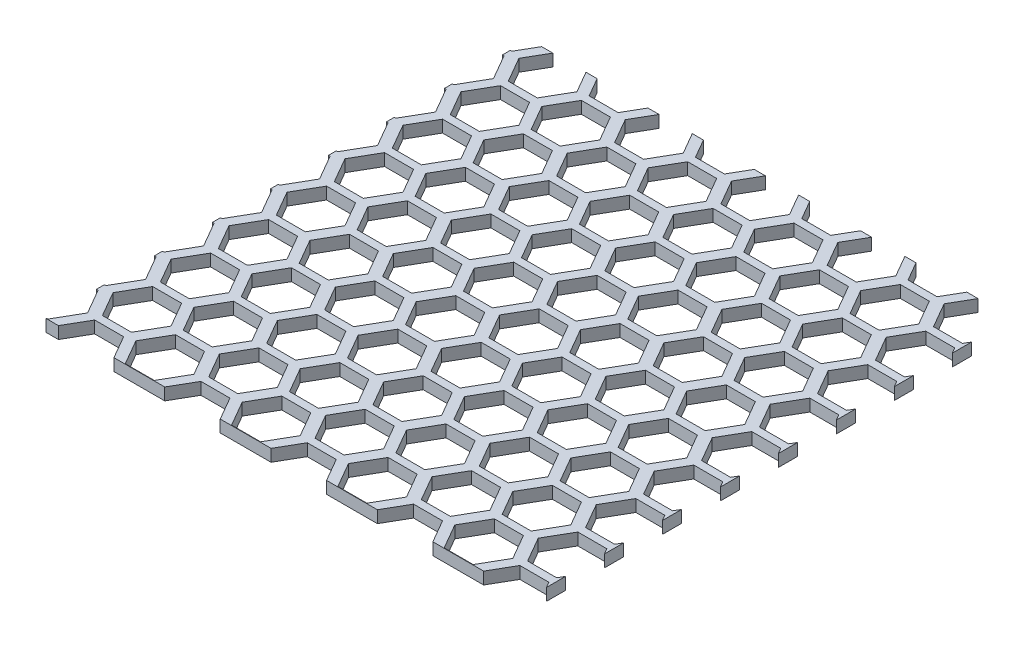
SolidWorks part; units mm, degrees
ref_plane "Front Plane" through (0, 0, 0) normal (0, 0, 1) x (1, 0, 0)
ref_plane "Top Plane" through (0, 0, 0) normal (0, 1, 0) x (1, 0, 0)
ref_plane "Right Plane" through (0, 0, 0) normal (1, 0, 0) x (0, 0, -1)
sketch "Sketch3" plane through (0, 0, 0) normal (0, 1, 0) x (1, 0, 0)
  line L0 (-647.1314, 0) -> (647.1314, 0) construction
  line L1 (131.9336, 512.7952) -> (101.9336, 564.7567)
  line L2 (101.9336, 564.7567) -> (41.9336, 564.7567)
  line L3 (41.9336, 564.7567) -> (11.9336, 512.7952)
  line L4 (11.9336, 512.7952) -> (41.9336, 460.8337)
  line L5 (41.9336, 460.8337) -> (101.9336, 460.8337)
  line L6 (101.9336, 460.8337) -> (131.9336, 512.7952)
  line L7 (241.9336, 455.4747) -> (211.9336, 507.4362)
  line L8 (211.9336, 507.4362) -> (151.9336, 507.4362)
  line L9 (151.9336, 507.4362) -> (121.9336, 455.4747)
  line L10 (121.9336, 455.4747) -> (151.9336, 403.5132)
  line L11 (151.9336, 403.5132) -> (211.9336, 403.5132)
  line L12 (211.9336, 403.5132) -> (241.9336, 455.4747)
  line L13 (351.9336, 512.7952) -> (321.9336, 564.7567)
  line L14 (321.9336, 564.7567) -> (261.9336, 564.7567)
  line L15 (261.9336, 564.7567) -> (231.9336, 512.7952)
  line L16 (231.9336, 512.7952) -> (261.9336, 460.8337)
  line L17 (261.9336, 460.8337) -> (321.9336, 460.8337)
  line L18 (321.9336, 460.8337) -> (351.9336, 512.7952)
  line L19 (461.9336, 455.4747) -> (431.9336, 507.4362)
  line L20 (431.9336, 507.4362) -> (371.9336, 507.4362)
  line L21 (371.9336, 507.4362) -> (341.9336, 455.4747)
  line L22 (341.9336, 455.4747) -> (371.9336, 403.5132)
  line L23 (371.9336, 403.5132) -> (431.9336, 403.5132)
  line L24 (431.9336, 403.5132) -> (461.9336, 455.4747)
  line L25 (571.9336, 512.7952) -> (541.9336, 564.7567)
  line L26 (541.9336, 564.7567) -> (481.9336, 564.7567)
  line L27 (481.9336, 564.7567) -> (451.9336, 512.7952)
  line L28 (451.9336, 512.7952) -> (481.9336, 460.8337)
  line L29 (481.9336, 460.8337) -> (541.9336, 460.8337)
  line L30 (541.9336, 460.8337) -> (571.9336, 512.7952)
  line L31 (681.9336, 455.4747) -> (651.9336, 507.4362)
  line L32 (651.9336, 507.4362) -> (591.9336, 507.4362)
  line L33 (591.9336, 507.4362) -> (561.9336, 455.4747)
  line L34 (561.9336, 455.4747) -> (591.9336, 403.5132)
  line L35 (591.9336, 403.5132) -> (651.9336, 403.5132)
  line L36 (651.9336, 403.5132) -> (681.9336, 455.4747)
  line L37 (791.9336, 512.7952) -> (761.9336, 564.7567)
  line L38 (761.9336, 564.7567) -> (701.9336, 564.7567)
  line L39 (701.9336, 564.7567) -> (671.9336, 512.7952)
  line L40 (671.9336, 512.7952) -> (701.9336, 460.8337)
  line L41 (701.9336, 460.8337) -> (761.9336, 460.8337)
  line L42 (761.9336, 460.8337) -> (791.9336, 512.7952)
  line L43 (901.9336, 455.4747) -> (871.9336, 507.4362)
  line L44 (871.9336, 507.4362) -> (811.9336, 507.4362)
  line L45 (811.9336, 507.4362) -> (781.9336, 455.4747)
  line L46 (781.9336, 455.4747) -> (811.9336, 403.5132)
  line L47 (811.9336, 403.5132) -> (871.9336, 403.5132)
  line L48 (871.9336, 403.5132) -> (901.9336, 455.4747)
  line L49 (1011.9336, 512.7952) -> (981.9336, 564.7567)
  line L50 (981.9336, 564.7567) -> (921.9336, 564.7567)
  line L51 (921.9336, 564.7567) -> (891.9336, 512.7952)
  line L52 (891.9336, 512.7952) -> (921.9336, 460.8337)
  line L53 (921.9336, 460.8337) -> (981.9336, 460.8337)
  line L54 (981.9336, 460.8337) -> (1011.9336, 512.7952)
  line L55 (1121.9336, 455.4747) -> (1091.9336, 507.4362)
  line L56 (1091.9336, 507.4362) -> (1031.9336, 507.4362)
  line L57 (1031.9336, 507.4362) -> (1001.9336, 455.4747)
  line L58 (1001.9336, 455.4747) -> (1031.9336, 403.5132)
  line L59 (1031.9336, 403.5132) -> (1091.9336, 403.5132)
  line L60 (1091.9336, 403.5132) -> (1121.9336, 455.4747)
  line L61 (1231.9336, 512.7952) -> (1201.9336, 564.7567)
  line L62 (1201.9336, 564.7567) -> (1141.9336, 564.7567)
  line L63 (1141.9336, 564.7567) -> (1111.9336, 512.7952)
  line L64 (1111.9336, 512.7952) -> (1141.9336, 460.8337)
  line L65 (1141.9336, 460.8337) -> (1201.9336, 460.8337)
  line L66 (1201.9336, 460.8337) -> (1231.9336, 512.7952)
  line L67 (1341.9336, 455.4747) -> (1311.9336, 507.4362)
  line L68 (1311.9336, 507.4362) -> (1251.9336, 507.4362)
  line L69 (1251.9336, 507.4362) -> (1221.9336, 455.4747)
  line L70 (1221.9336, 455.4747) -> (1251.9336, 403.5132)
  line L71 (1251.9336, 403.5132) -> (1311.9336, 403.5132)
  line L72 (1311.9336, 403.5132) -> (1341.9336, 455.4747)
  line L73 (351.9336, 392.7952) -> (321.9336, 444.7567)
  line L74 (321.9336, 444.7567) -> (261.9336, 444.7567)
  line L75 (261.9336, 444.7567) -> (231.9336, 392.7952)
  line L76 (231.9336, 392.7952) -> (261.9336, 340.8337)
  line L77 (261.9336, 340.8337) -> (321.9336, 340.8337)
  line L78 (321.9336, 340.8337) -> (351.9336, 392.7952)
  line L79 (461.9336, 335.4747) -> (431.9336, 387.4362)
  line L80 (431.9336, 387.4362) -> (371.9336, 387.4362)
  line L81 (371.9336, 387.4362) -> (341.9336, 335.4747)
  line L82 (341.9336, 335.4747) -> (371.9336, 283.5132)
  line L83 (371.9336, 283.5132) -> (431.9336, 283.5132)
  line L84 (431.9336, 283.5132) -> (461.9336, 335.4747)
  line L85 (571.9336, 392.7952) -> (541.9336, 444.7567)
  line L86 (541.9336, 444.7567) -> (481.9336, 444.7567)
  line L87 (481.9336, 444.7567) -> (451.9336, 392.7952)
  line L88 (451.9336, 392.7952) -> (481.9336, 340.8337)
  line L89 (481.9336, 340.8337) -> (541.9336, 340.8337)
  line L90 (541.9336, 340.8337) -> (571.9336, 392.7952)
  line L91 (681.9336, 335.4747) -> (651.9336, 387.4362)
  line L92 (651.9336, 387.4362) -> (591.9336, 387.4362)
  line L93 (591.9336, 387.4362) -> (561.9336, 335.4747)
  line L94 (561.9336, 335.4747) -> (591.9336, 283.5132)
  line L95 (591.9336, 283.5132) -> (651.9336, 283.5132)
  line L96 (651.9336, 283.5132) -> (681.9336, 335.4747)
  line L97 (791.9336, 392.7952) -> (761.9336, 444.7567)
  line L98 (761.9336, 444.7567) -> (701.9336, 444.7567)
  line L99 (701.9336, 444.7567) -> (671.9336, 392.7952)
  line L100 (671.9336, 392.7952) -> (701.9336, 340.8337)
  line L101 (701.9336, 340.8337) -> (761.9336, 340.8337)
  line L102 (761.9336, 340.8337) -> (791.9336, 392.7952)
  line L103 (901.9336, 335.4747) -> (871.9336, 387.4362)
  line L104 (871.9336, 387.4362) -> (811.9336, 387.4362)
  line L105 (811.9336, 387.4362) -> (781.9336, 335.4747)
  line L106 (781.9336, 335.4747) -> (811.9336, 283.5132)
  line L107 (811.9336, 283.5132) -> (871.9336, 283.5132)
  line L108 (871.9336, 283.5132) -> (901.9336, 335.4747)
  line L109 (1011.9336, 392.7952) -> (981.9336, 444.7567)
  line L110 (981.9336, 444.7567) -> (921.9336, 444.7567)
  line L111 (921.9336, 444.7567) -> (891.9336, 392.7952)
  line L112 (891.9336, 392.7952) -> (921.9336, 340.8337)
  line L113 (921.9336, 340.8337) -> (981.9336, 340.8337)
  line L114 (981.9336, 340.8337) -> (1011.9336, 392.7952)
  line L115 (1121.9336, 335.4747) -> (1091.9336, 387.4362)
  line L116 (1091.9336, 387.4362) -> (1031.9336, 387.4362)
  line L117 (1031.9336, 387.4362) -> (1001.9336, 335.4747)
  line L118 (1001.9336, 335.4747) -> (1031.9336, 283.5132)
  line L119 (1031.9336, 283.5132) -> (1091.9336, 283.5132)
  line L120 (1091.9336, 283.5132) -> (1121.9336, 335.4747)
  line L121 (1231.9336, 392.7952) -> (1201.9336, 444.7567)
  line L122 (1201.9336, 444.7567) -> (1141.9336, 444.7567)
  line L123 (1141.9336, 444.7567) -> (1111.9336, 392.7952)
  line L124 (1111.9336, 392.7952) -> (1141.9336, 340.8337)
  line L125 (1141.9336, 340.8337) -> (1201.9336, 340.8337)
  line L126 (1201.9336, 340.8337) -> (1231.9336, 392.7952)
  line L127 (1341.9336, 335.4747) -> (1311.9336, 387.4362)
  line L128 (1311.9336, 387.4362) -> (1251.9336, 387.4362)
  line L129 (1251.9336, 387.4362) -> (1221.9336, 335.4747)
  line L130 (1221.9336, 335.4747) -> (1251.9336, 283.5132)
  line L131 (1251.9336, 283.5132) -> (1311.9336, 283.5132)
  line L132 (1311.9336, 283.5132) -> (1341.9336, 335.4747)
  line L133 (351.9336, 272.7952) -> (321.9336, 324.7567)
  line L134 (321.9336, 324.7567) -> (261.9336, 324.7567)
  line L135 (261.9336, 324.7567) -> (231.9336, 272.7952)
  line L136 (231.9336, 272.7952) -> (261.9336, 220.8337)
  line L137 (261.9336, 220.8337) -> (321.9336, 220.8337)
  line L138 (321.9336, 220.8337) -> (351.9336, 272.7952)
  line L139 (461.9336, 215.4747) -> (431.9336, 267.4362)
  line L140 (431.9336, 267.4362) -> (371.9336, 267.4362)
  line L141 (371.9336, 267.4362) -> (341.9336, 215.4747)
  line L142 (341.9336, 215.4747) -> (371.9336, 163.5132)
  line L143 (371.9336, 163.5132) -> (431.9336, 163.5132)
  line L144 (431.9336, 163.5132) -> (461.9336, 215.4747)
  line L145 (571.9336, 272.7952) -> (541.9336, 324.7567)
  line L146 (541.9336, 324.7567) -> (481.9336, 324.7567)
  line L147 (481.9336, 324.7567) -> (451.9336, 272.7952)
  line L148 (451.9336, 272.7952) -> (481.9336, 220.8337)
  line L149 (481.9336, 220.8337) -> (541.9336, 220.8337)
  line L150 (541.9336, 220.8337) -> (571.9336, 272.7952)
  line L151 (681.9336, 215.4747) -> (651.9336, 267.4362)
  line L152 (651.9336, 267.4362) -> (591.9336, 267.4362)
  line L153 (591.9336, 267.4362) -> (561.9336, 215.4747)
  line L154 (561.9336, 215.4747) -> (591.9336, 163.5132)
  line L155 (591.9336, 163.5132) -> (651.9336, 163.5132)
  line L156 (651.9336, 163.5132) -> (681.9336, 215.4747)
  line L157 (791.9336, 272.7952) -> (761.9336, 324.7567)
  line L158 (761.9336, 324.7567) -> (701.9336, 324.7567)
  line L159 (701.9336, 324.7567) -> (671.9336, 272.7952)
  line L160 (671.9336, 272.7952) -> (701.9336, 220.8337)
  line L161 (701.9336, 220.8337) -> (761.9336, 220.8337)
  line L162 (761.9336, 220.8337) -> (791.9336, 272.7952)
  line L163 (901.9336, 215.4747) -> (871.9336, 267.4362)
  line L164 (871.9336, 267.4362) -> (811.9336, 267.4362)
  line L165 (811.9336, 267.4362) -> (781.9336, 215.4747)
  line L166 (781.9336, 215.4747) -> (811.9336, 163.5132)
  line L167 (811.9336, 163.5132) -> (871.9336, 163.5132)
  line L168 (871.9336, 163.5132) -> (901.9336, 215.4747)
  line L169 (1011.9336, 272.7952) -> (981.9336, 324.7567)
  line L170 (981.9336, 324.7567) -> (921.9336, 324.7567)
  line L171 (921.9336, 324.7567) -> (891.9336, 272.7952)
  line L172 (891.9336, 272.7952) -> (921.9336, 220.8337)
  line L173 (921.9336, 220.8337) -> (981.9336, 220.8337)
  line L174 (981.9336, 220.8337) -> (1011.9336, 272.7952)
  line L175 (1121.9336, 215.4747) -> (1091.9336, 267.4362)
  line L176 (1091.9336, 267.4362) -> (1031.9336, 267.4362)
  line L177 (1031.9336, 267.4362) -> (1001.9336, 215.4747)
  line L178 (1001.9336, 215.4747) -> (1031.9336, 163.5132)
  line L179 (1031.9336, 163.5132) -> (1091.9336, 163.5132)
  line L180 (1091.9336, 163.5132) -> (1121.9336, 215.4747)
  line L181 (1231.9336, 272.7952) -> (1201.9336, 324.7567)
  line L182 (1201.9336, 324.7567) -> (1141.9336, 324.7567)
  line L183 (1141.9336, 324.7567) -> (1111.9336, 272.7952)
  line L184 (1111.9336, 272.7952) -> (1141.9336, 220.8337)
  line L185 (1141.9336, 220.8337) -> (1201.9336, 220.8337)
  line L186 (1201.9336, 220.8337) -> (1231.9336, 272.7952)
  line L187 (1341.9336, 215.4747) -> (1311.9336, 267.4362)
  line L188 (1311.9336, 267.4362) -> (1251.9336, 267.4362)
  line L189 (1251.9336, 267.4362) -> (1221.9336, 215.4747)
  line L190 (1221.9336, 215.4747) -> (1251.9336, 163.5132)
  line L191 (1251.9336, 163.5132) -> (1311.9336, 163.5132)
  line L192 (1311.9336, 163.5132) -> (1341.9336, 215.4747)
  line L193 (351.9336, 152.7952) -> (321.9336, 204.7567)
  line L194 (321.9336, 204.7567) -> (261.9336, 204.7567)
  line L195 (261.9336, 204.7567) -> (231.9336, 152.7952)
  line L196 (231.9336, 152.7952) -> (261.9336, 100.8337)
  line L197 (261.9336, 100.8337) -> (321.9336, 100.8337)
  line L198 (321.9336, 100.8337) -> (351.9336, 152.7952)
  line L199 (461.9336, 95.4747) -> (431.9336, 147.4362)
  line L200 (431.9336, 147.4362) -> (371.9336, 147.4362)
  line L201 (371.9336, 147.4362) -> (341.9336, 95.4747)
  line L202 (341.9336, 95.4747) -> (371.9336, 43.5132)
  line L203 (371.9336, 43.5132) -> (431.9336, 43.5132)
  line L204 (431.9336, 43.5132) -> (461.9336, 95.4747)
  line L205 (571.9336, 152.7952) -> (541.9336, 204.7567)
  line L206 (541.9336, 204.7567) -> (481.9336, 204.7567)
  line L207 (481.9336, 204.7567) -> (451.9336, 152.7952)
  line L208 (451.9336, 152.7952) -> (481.9336, 100.8337)
  line L209 (481.9336, 100.8337) -> (541.9336, 100.8337)
  line L210 (541.9336, 100.8337) -> (571.9336, 152.7952)
  line L211 (681.9336, 95.4747) -> (651.9336, 147.4362)
  line L212 (651.9336, 147.4362) -> (591.9336, 147.4362)
  line L213 (591.9336, 147.4362) -> (561.9336, 95.4747)
  line L214 (561.9336, 95.4747) -> (591.9336, 43.5132)
  line L215 (591.9336, 43.5132) -> (651.9336, 43.5132)
  line L216 (651.9336, 43.5132) -> (681.9336, 95.4747)
  line L217 (791.9336, 152.7952) -> (761.9336, 204.7567)
  line L218 (761.9336, 204.7567) -> (701.9336, 204.7567)
  line L219 (701.9336, 204.7567) -> (671.9336, 152.7952)
  line L220 (671.9336, 152.7952) -> (701.9336, 100.8337)
  line L221 (701.9336, 100.8337) -> (761.9336, 100.8337)
  line L222 (761.9336, 100.8337) -> (791.9336, 152.7952)
  line L223 (901.9336, 95.4747) -> (871.9336, 147.4362)
  line L224 (871.9336, 147.4362) -> (811.9336, 147.4362)
  line L225 (811.9336, 147.4362) -> (781.9336, 95.4747)
  line L226 (781.9336, 95.4747) -> (811.9336, 43.5132)
  line L227 (811.9336, 43.5132) -> (871.9336, 43.5132)
  line L228 (871.9336, 43.5132) -> (901.9336, 95.4747)
  line L229 (1011.9336, 152.7952) -> (981.9336, 204.7567)
  line L230 (981.9336, 204.7567) -> (921.9336, 204.7567)
  line L231 (921.9336, 204.7567) -> (891.9336, 152.7952)
  line L232 (891.9336, 152.7952) -> (921.9336, 100.8337)
  line L233 (921.9336, 100.8337) -> (981.9336, 100.8337)
  line L234 (981.9336, 100.8337) -> (1011.9336, 152.7952)
  line L235 (1121.9336, 95.4747) -> (1091.9336, 147.4362)
  line L236 (1091.9336, 147.4362) -> (1031.9336, 147.4362)
  line L237 (1031.9336, 147.4362) -> (1001.9336, 95.4747)
  line L238 (1001.9336, 95.4747) -> (1031.9336, 43.5132)
  line L239 (1031.9336, 43.5132) -> (1091.9336, 43.5132)
  line L240 (1091.9336, 43.5132) -> (1121.9336, 95.4747)
  line L241 (1231.9336, 152.7952) -> (1201.9336, 204.7567)
  line L242 (1201.9336, 204.7567) -> (1141.9336, 204.7567)
  line L243 (1141.9336, 204.7567) -> (1111.9336, 152.7952)
  line L244 (1111.9336, 152.7952) -> (1141.9336, 100.8337)
  line L245 (1141.9336, 100.8337) -> (1201.9336, 100.8337)
  line L246 (1201.9336, 100.8337) -> (1231.9336, 152.7952)
  line L247 (1341.9336, 95.4747) -> (1311.9336, 147.4362)
  line L248 (1311.9336, 147.4362) -> (1251.9336, 147.4362)
  line L249 (1251.9336, 147.4362) -> (1221.9336, 95.4747)
  line L250 (1221.9336, 95.4747) -> (1251.9336, 43.5132)
  line L251 (1251.9336, 43.5132) -> (1311.9336, 43.5132)
  line L252 (1311.9336, 43.5132) -> (1341.9336, 95.4747)
  line L253 (351.9336, 32.7952) -> (321.9336, 84.7567)
  line L254 (321.9336, 84.7567) -> (261.9336, 84.7567)
  line L255 (261.9336, 84.7567) -> (231.9336, 32.7952)
  line L256 (231.9336, 32.7952) -> (261.9336, -19.1663)
  line L257 (261.9336, -19.1663) -> (321.9336, -19.1663)
  line L258 (321.9336, -19.1663) -> (351.9336, 32.7952)
  line L259 (461.9336, -24.5253) -> (431.9336, 27.4362)
  line L260 (431.9336, 27.4362) -> (371.9336, 27.4362)
  line L261 (371.9336, 27.4362) -> (341.9336, -24.5253)
  line L262 (341.9336, -24.5253) -> (371.9336, -76.4868)
  line L263 (371.9336, -76.4868) -> (431.9336, -76.4868)
  line L264 (431.9336, -76.4868) -> (461.9336, -24.5253)
  line L265 (571.9336, 32.7952) -> (541.9336, 84.7567)
  line L266 (541.9336, 84.7567) -> (481.9336, 84.7567)
  line L267 (481.9336, 84.7567) -> (451.9336, 32.7952)
  line L268 (451.9336, 32.7952) -> (481.9336, -19.1663)
  line L269 (481.9336, -19.1663) -> (541.9336, -19.1663)
  line L270 (541.9336, -19.1663) -> (571.9336, 32.7952)
  line L271 (681.9336, -24.5253) -> (651.9336, 27.4362)
  line L272 (651.9336, 27.4362) -> (591.9336, 27.4362)
  line L273 (591.9336, 27.4362) -> (561.9336, -24.5253)
  line L274 (561.9336, -24.5253) -> (591.9336, -76.4868)
  line L275 (591.9336, -76.4868) -> (651.9336, -76.4868)
  line L276 (651.9336, -76.4868) -> (681.9336, -24.5253)
  line L277 (791.9336, 32.7952) -> (761.9336, 84.7567)
  line L278 (761.9336, 84.7567) -> (701.9336, 84.7567)
  line L279 (701.9336, 84.7567) -> (671.9336, 32.7952)
  line L280 (671.9336, 32.7952) -> (701.9336, -19.1663)
  line L281 (701.9336, -19.1663) -> (761.9336, -19.1663)
  line L282 (761.9336, -19.1663) -> (791.9336, 32.7952)
  line L283 (901.9336, -24.5253) -> (871.9336, 27.4362)
  line L284 (871.9336, 27.4362) -> (811.9336, 27.4362)
  line L285 (811.9336, 27.4362) -> (781.9336, -24.5253)
  line L286 (781.9336, -24.5253) -> (811.9336, -76.4868)
  line L287 (811.9336, -76.4868) -> (871.9336, -76.4868)
  line L288 (871.9336, -76.4868) -> (901.9336, -24.5253)
  line L289 (1011.9336, 32.7952) -> (981.9336, 84.7567)
  line L290 (981.9336, 84.7567) -> (921.9336, 84.7567)
  line L291 (921.9336, 84.7567) -> (891.9336, 32.7952)
  line L292 (891.9336, 32.7952) -> (921.9336, -19.1663)
  line L293 (921.9336, -19.1663) -> (981.9336, -19.1663)
  line L294 (981.9336, -19.1663) -> (1011.9336, 32.7952)
  line L295 (1121.9336, -24.5253) -> (1091.9336, 27.4362)
  line L296 (1091.9336, 27.4362) -> (1031.9336, 27.4362)
  line L297 (1031.9336, 27.4362) -> (1001.9336, -24.5253)
  line L298 (1001.9336, -24.5253) -> (1031.9336, -76.4868)
  line L299 (1031.9336, -76.4868) -> (1091.9336, -76.4868)
  line L300 (1091.9336, -76.4868) -> (1121.9336, -24.5253)
  line L301 (1231.9336, 32.7952) -> (1201.9336, 84.7567)
  line L302 (1201.9336, 84.7567) -> (1141.9336, 84.7567)
  line L303 (1141.9336, 84.7567) -> (1111.9336, 32.7952)
  line L304 (1111.9336, 32.7952) -> (1141.9336, -19.1663)
  line L305 (1141.9336, -19.1663) -> (1201.9336, -19.1663)
  line L306 (1201.9336, -19.1663) -> (1231.9336, 32.7952)
  line L307 (1341.9336, -24.5253) -> (1311.9336, 27.4362)
  line L308 (1311.9336, 27.4362) -> (1251.9336, 27.4362)
  line L309 (1251.9336, 27.4362) -> (1221.9336, -24.5253)
  line L310 (1221.9336, -24.5253) -> (1251.9336, -76.4868)
  line L311 (1251.9336, -76.4868) -> (1311.9336, -76.4868)
  line L312 (1311.9336, -76.4868) -> (1341.9336, -24.5253)
  line L313 (351.9336, -87.2048) -> (321.9336, -35.2433)
  line L314 (321.9336, -35.2433) -> (261.9336, -35.2433)
  line L315 (261.9336, -35.2433) -> (231.9336, -87.2048)
  line L316 (231.9336, -87.2048) -> (261.9336, -139.1663)
  line L317 (261.9336, -139.1663) -> (321.9336, -139.1663)
  line L318 (321.9336, -139.1663) -> (351.9336, -87.2048)
  line L319 (461.9336, -144.5253) -> (431.9336, -92.5638)
  line L320 (431.9336, -92.5638) -> (371.9336, -92.5638)
  line L321 (371.9336, -92.5638) -> (341.9336, -144.5253)
  line L322 (341.9336, -144.5253) -> (371.9336, -196.4868)
  line L323 (371.9336, -196.4868) -> (431.9336, -196.4868)
  line L324 (431.9336, -196.4868) -> (461.9336, -144.5253)
  line L325 (571.9336, -87.2048) -> (541.9336, -35.2433)
  line L326 (541.9336, -35.2433) -> (481.9336, -35.2433)
  line L327 (481.9336, -35.2433) -> (451.9336, -87.2048)
  line L328 (451.9336, -87.2048) -> (481.9336, -139.1663)
  line L329 (481.9336, -139.1663) -> (541.9336, -139.1663)
  line L330 (541.9336, -139.1663) -> (571.9336, -87.2048)
  line L331 (681.9336, -144.5253) -> (651.9336, -92.5638)
  line L332 (651.9336, -92.5638) -> (591.9336, -92.5638)
  line L333 (591.9336, -92.5638) -> (561.9336, -144.5253)
  line L334 (561.9336, -144.5253) -> (591.9336, -196.4868)
  line L335 (591.9336, -196.4868) -> (651.9336, -196.4868)
  line L336 (651.9336, -196.4868) -> (681.9336, -144.5253)
  line L337 (791.9336, -87.2048) -> (761.9336, -35.2433)
  line L338 (761.9336, -35.2433) -> (701.9336, -35.2433)
  line L339 (701.9336, -35.2433) -> (671.9336, -87.2048)
  line L340 (671.9336, -87.2048) -> (701.9336, -139.1663)
  line L341 (701.9336, -139.1663) -> (761.9336, -139.1663)
  line L342 (761.9336, -139.1663) -> (791.9336, -87.2048)
  line L343 (901.9336, -144.5253) -> (871.9336, -92.5638)
  line L344 (871.9336, -92.5638) -> (811.9336, -92.5638)
  line L345 (811.9336, -92.5638) -> (781.9336, -144.5253)
  line L346 (781.9336, -144.5253) -> (811.9336, -196.4868)
  line L347 (811.9336, -196.4868) -> (871.9336, -196.4868)
  line L348 (871.9336, -196.4868) -> (901.9336, -144.5253)
  line L349 (1011.9336, -87.2048) -> (981.9336, -35.2433)
  line L350 (981.9336, -35.2433) -> (921.9336, -35.2433)
  line L351 (921.9336, -35.2433) -> (891.9336, -87.2048)
  line L352 (891.9336, -87.2048) -> (921.9336, -139.1663)
  line L353 (921.9336, -139.1663) -> (981.9336, -139.1663)
  line L354 (981.9336, -139.1663) -> (1011.9336, -87.2048)
  line L355 (1121.9336, -144.5253) -> (1091.9336, -92.5638)
  line L356 (1091.9336, -92.5638) -> (1031.9336, -92.5638)
  line L357 (1031.9336, -92.5638) -> (1001.9336, -144.5253)
  line L358 (1001.9336, -144.5253) -> (1031.9336, -196.4868)
  line L359 (1031.9336, -196.4868) -> (1091.9336, -196.4868)
  line L360 (1091.9336, -196.4868) -> (1121.9336, -144.5253)
  line L361 (1231.9336, -87.2048) -> (1201.9336, -35.2433)
  line L362 (1201.9336, -35.2433) -> (1141.9336, -35.2433)
  line L363 (1141.9336, -35.2433) -> (1111.9336, -87.2048)
  line L364 (1111.9336, -87.2048) -> (1141.9336, -139.1663)
  line L365 (1141.9336, -139.1663) -> (1201.9336, -139.1663)
  line L366 (1201.9336, -139.1663) -> (1231.9336, -87.2048)
  line L367 (1341.9336, -144.5253) -> (1311.9336, -92.5638)
  line L368 (1311.9336, -92.5638) -> (1251.9336, -92.5638)
  line L369 (1251.9336, -92.5638) -> (1221.9336, -144.5253)
  line L370 (1221.9336, -144.5253) -> (1251.9336, -196.4868)
  line L371 (1251.9336, -196.4868) -> (1311.9336, -196.4868)
  line L372 (1311.9336, -196.4868) -> (1341.9336, -144.5253)
  line L373 (351.9336, -207.2048) -> (321.9336, -155.2433)
  line L374 (321.9336, -155.2433) -> (261.9336, -155.2433)
  line L375 (261.9336, -155.2433) -> (231.9336, -207.2048)
  line L376 (231.9336, -207.2048) -> (261.9336, -259.1663)
  line L377 (261.9336, -259.1663) -> (321.9336, -259.1663)
  line L378 (321.9336, -259.1663) -> (351.9336, -207.2048)
  line L379 (461.9336, -264.5253) -> (431.9336, -212.5638)
  line L380 (431.9336, -212.5638) -> (371.9336, -212.5638)
  line L381 (371.9336, -212.5638) -> (341.9336, -264.5253)
  line L382 (341.9336, -264.5253) -> (371.9336, -316.4868)
  line L383 (371.9336, -316.4868) -> (431.9336, -316.4868)
  line L384 (431.9336, -316.4868) -> (461.9336, -264.5253)
  line L385 (571.9336, -207.2048) -> (541.9336, -155.2433)
  line L386 (541.9336, -155.2433) -> (481.9336, -155.2433)
  line L387 (481.9336, -155.2433) -> (451.9336, -207.2048)
  line L388 (451.9336, -207.2048) -> (481.9336, -259.1663)
  line L389 (481.9336, -259.1663) -> (541.9336, -259.1663)
  line L390 (541.9336, -259.1663) -> (571.9336, -207.2048)
  line L391 (681.9336, -264.5253) -> (651.9336, -212.5638)
  line L392 (651.9336, -212.5638) -> (591.9336, -212.5638)
  line L393 (591.9336, -212.5638) -> (561.9336, -264.5253)
  line L394 (561.9336, -264.5253) -> (591.9336, -316.4868)
  line L395 (591.9336, -316.4868) -> (651.9336, -316.4868)
  line L396 (651.9336, -316.4868) -> (681.9336, -264.5253)
  line L397 (791.9336, -207.2048) -> (761.9336, -155.2433)
  line L398 (761.9336, -155.2433) -> (701.9336, -155.2433)
  line L399 (701.9336, -155.2433) -> (671.9336, -207.2048)
  line L400 (671.9336, -207.2048) -> (701.9336, -259.1663)
  line L401 (701.9336, -259.1663) -> (761.9336, -259.1663)
  line L402 (761.9336, -259.1663) -> (791.9336, -207.2048)
  line L403 (901.9336, -264.5253) -> (871.9336, -212.5638)
  line L404 (871.9336, -212.5638) -> (811.9336, -212.5638)
  line L405 (811.9336, -212.5638) -> (781.9336, -264.5253)
  line L406 (781.9336, -264.5253) -> (811.9336, -316.4868)
  line L407 (811.9336, -316.4868) -> (871.9336, -316.4868)
  line L408 (871.9336, -316.4868) -> (901.9336, -264.5253)
  line L409 (1011.9336, -207.2048) -> (981.9336, -155.2433)
  line L410 (981.9336, -155.2433) -> (921.9336, -155.2433)
  line L411 (921.9336, -155.2433) -> (891.9336, -207.2048)
  line L412 (891.9336, -207.2048) -> (921.9336, -259.1663)
  line L413 (921.9336, -259.1663) -> (981.9336, -259.1663)
  line L414 (981.9336, -259.1663) -> (1011.9336, -207.2048)
  line L415 (1121.9336, -264.5253) -> (1091.9336, -212.5638)
  line L416 (1091.9336, -212.5638) -> (1031.9336, -212.5638)
  line L417 (1031.9336, -212.5638) -> (1001.9336, -264.5253)
  line L418 (1001.9336, -264.5253) -> (1031.9336, -316.4868)
  line L419 (1031.9336, -316.4868) -> (1091.9336, -316.4868)
  line L420 (1091.9336, -316.4868) -> (1121.9336, -264.5253)
  line L421 (1231.9336, -207.2048) -> (1201.9336, -155.2433)
  line L422 (1201.9336, -155.2433) -> (1141.9336, -155.2433)
  line L423 (1141.9336, -155.2433) -> (1111.9336, -207.2048)
  line L424 (1111.9336, -207.2048) -> (1141.9336, -259.1663)
  line L425 (1141.9336, -259.1663) -> (1201.9336, -259.1663)
  line L426 (1201.9336, -259.1663) -> (1231.9336, -207.2048)
  line L427 (1341.9336, -264.5253) -> (1311.9336, -212.5638)
  line L428 (1311.9336, -212.5638) -> (1251.9336, -212.5638)
  line L429 (1251.9336, -212.5638) -> (1221.9336, -264.5253)
  line L430 (1221.9336, -264.5253) -> (1251.9336, -316.4868)
  line L431 (1251.9336, -316.4868) -> (1311.9336, -316.4868)
  line L432 (1311.9336, -316.4868) -> (1341.9336, -264.5253)
  line L433 (351.9336, -327.2048) -> (321.9336, -275.2433)
  line L434 (321.9336, -275.2433) -> (261.9336, -275.2433)
  line L435 (261.9336, -275.2433) -> (231.9336, -327.2048)
  line L436 (231.9336, -327.2048) -> (261.9336, -379.1663)
  line L437 (261.9336, -379.1663) -> (321.9336, -379.1663)
  line L438 (321.9336, -379.1663) -> (351.9336, -327.2048)
  line L439 (461.9336, -384.5253) -> (431.9336, -332.5638)
  line L440 (431.9336, -332.5638) -> (371.9336, -332.5638)
  line L441 (371.9336, -332.5638) -> (341.9336, -384.5253)
  line L442 (341.9336, -384.5253) -> (371.9336, -436.4868)
  line L443 (371.9336, -436.4868) -> (431.9336, -436.4868)
  line L444 (431.9336, -436.4868) -> (461.9336, -384.5253)
  line L445 (571.9336, -327.2048) -> (541.9336, -275.2433)
  line L446 (541.9336, -275.2433) -> (481.9336, -275.2433)
  line L447 (481.9336, -275.2433) -> (451.9336, -327.2048)
  line L448 (451.9336, -327.2048) -> (481.9336, -379.1663)
  line L449 (481.9336, -379.1663) -> (541.9336, -379.1663)
  line L450 (541.9336, -379.1663) -> (571.9336, -327.2048)
  line L451 (681.9336, -384.5253) -> (651.9336, -332.5638)
  line L452 (651.9336, -332.5638) -> (591.9336, -332.5638)
  line L453 (591.9336, -332.5638) -> (561.9336, -384.5253)
  line L454 (561.9336, -384.5253) -> (591.9336, -436.4868)
  line L455 (591.9336, -436.4868) -> (651.9336, -436.4868)
  line L456 (651.9336, -436.4868) -> (681.9336, -384.5253)
  line L457 (791.9336, -327.2048) -> (761.9336, -275.2433)
  line L458 (761.9336, -275.2433) -> (701.9336, -275.2433)
  line L459 (701.9336, -275.2433) -> (671.9336, -327.2048)
  line L460 (671.9336, -327.2048) -> (701.9336, -379.1663)
  line L461 (701.9336, -379.1663) -> (761.9336, -379.1663)
  line L462 (761.9336, -379.1663) -> (791.9336, -327.2048)
  line L463 (901.9336, -384.5253) -> (871.9336, -332.5638)
  line L464 (871.9336, -332.5638) -> (811.9336, -332.5638)
  line L465 (811.9336, -332.5638) -> (781.9336, -384.5253)
  line L466 (781.9336, -384.5253) -> (811.9336, -436.4868)
  line L467 (811.9336, -436.4868) -> (871.9336, -436.4868)
  line L468 (871.9336, -436.4868) -> (901.9336, -384.5253)
  line L469 (1011.9336, -327.2048) -> (981.9336, -275.2433)
  line L470 (981.9336, -275.2433) -> (921.9336, -275.2433)
  line L471 (921.9336, -275.2433) -> (891.9336, -327.2048)
  line L472 (891.9336, -327.2048) -> (921.9336, -379.1663)
  line L473 (921.9336, -379.1663) -> (981.9336, -379.1663)
  line L474 (981.9336, -379.1663) -> (1011.9336, -327.2048)
  line L475 (1121.9336, -384.5253) -> (1091.9336, -332.5638)
  line L476 (1091.9336, -332.5638) -> (1031.9336, -332.5638)
  line L477 (1031.9336, -332.5638) -> (1001.9336, -384.5253)
  line L478 (1001.9336, -384.5253) -> (1031.9336, -436.4868)
  line L479 (1031.9336, -436.4868) -> (1091.9336, -436.4868)
  line L480 (1091.9336, -436.4868) -> (1121.9336, -384.5253)
  line L481 (1231.9336, -327.2048) -> (1201.9336, -275.2433)
  line L482 (1201.9336, -275.2433) -> (1141.9336, -275.2433)
  line L483 (1141.9336, -275.2433) -> (1111.9336, -327.2048)
  line L484 (1111.9336, -327.2048) -> (1141.9336, -379.1663)
  line L485 (1141.9336, -379.1663) -> (1201.9336, -379.1663)
  line L486 (1201.9336, -379.1663) -> (1231.9336, -327.2048)
  line L487 (1341.9336, -384.5253) -> (1311.9336, -332.5638)
  line L488 (1311.9336, -332.5638) -> (1251.9336, -332.5638)
  line L489 (1251.9336, -332.5638) -> (1221.9336, -384.5253)
  line L490 (1221.9336, -384.5253) -> (1251.9336, -436.4868)
  line L491 (1251.9336, -436.4868) -> (1311.9336, -436.4868)
  line L492 (1311.9336, -436.4868) -> (1341.9336, -384.5253)
  line L493 (351.9336, -447.2048) -> (321.9336, -395.2433)
  line L494 (321.9336, -395.2433) -> (261.9336, -395.2433)
  line L495 (261.9336, -395.2433) -> (231.9336, -447.2048)
  line L496 (231.9336, -447.2048) -> (261.9336, -499.1663)
  line L497 (261.9336, -499.1663) -> (321.9336, -499.1663)
  line L498 (321.9336, -499.1663) -> (351.9336, -447.2048)
  line L499 (461.9336, -504.5253) -> (431.9336, -452.5638)
  line L500 (431.9336, -452.5638) -> (371.9336, -452.5638)
  line L501 (371.9336, -452.5638) -> (341.9336, -504.5253)
  line L502 (341.9336, -504.5253) -> (371.9336, -556.4868)
  line L503 (371.9336, -556.4868) -> (431.9336, -556.4868)
  line L504 (431.9336, -556.4868) -> (461.9336, -504.5253)
  line L505 (571.9336, -447.2048) -> (541.9336, -395.2433)
  line L506 (541.9336, -395.2433) -> (481.9336, -395.2433)
  line L507 (481.9336, -395.2433) -> (451.9336, -447.2048)
  line L508 (451.9336, -447.2048) -> (481.9336, -499.1663)
  line L509 (481.9336, -499.1663) -> (541.9336, -499.1663)
  line L510 (541.9336, -499.1663) -> (571.9336, -447.2048)
  line L511 (681.9336, -504.5253) -> (651.9336, -452.5638)
  line L512 (651.9336, -452.5638) -> (591.9336, -452.5638)
  line L513 (591.9336, -452.5638) -> (561.9336, -504.5253)
  line L514 (561.9336, -504.5253) -> (591.9336, -556.4868)
  line L515 (591.9336, -556.4868) -> (651.9336, -556.4868)
  line L516 (651.9336, -556.4868) -> (681.9336, -504.5253)
  line L517 (791.9336, -447.2048) -> (761.9336, -395.2433)
  line L518 (761.9336, -395.2433) -> (701.9336, -395.2433)
  line L519 (701.9336, -395.2433) -> (671.9336, -447.2048)
  line L520 (671.9336, -447.2048) -> (701.9336, -499.1663)
  line L521 (701.9336, -499.1663) -> (761.9336, -499.1663)
  line L522 (761.9336, -499.1663) -> (791.9336, -447.2048)
  line L523 (901.9336, -504.5253) -> (871.9336, -452.5638)
  line L524 (871.9336, -452.5638) -> (811.9336, -452.5638)
  line L525 (811.9336, -452.5638) -> (781.9336, -504.5253)
  line L526 (781.9336, -504.5253) -> (811.9336, -556.4868)
  line L527 (811.9336, -556.4868) -> (871.9336, -556.4868)
  line L528 (871.9336, -556.4868) -> (901.9336, -504.5253)
  line L529 (1011.9336, -447.2048) -> (981.9336, -395.2433)
  line L530 (981.9336, -395.2433) -> (921.9336, -395.2433)
  line L531 (921.9336, -395.2433) -> (891.9336, -447.2048)
  line L532 (891.9336, -447.2048) -> (921.9336, -499.1663)
  line L533 (921.9336, -499.1663) -> (981.9336, -499.1663)
  line L534 (981.9336, -499.1663) -> (1011.9336, -447.2048)
  line L535 (1121.9336, -504.5253) -> (1091.9336, -452.5638)
  line L536 (1091.9336, -452.5638) -> (1031.9336, -452.5638)
  line L537 (1031.9336, -452.5638) -> (1001.9336, -504.5253)
  line L538 (1001.9336, -504.5253) -> (1031.9336, -556.4868)
  line L539 (1031.9336, -556.4868) -> (1091.9336, -556.4868)
  line L540 (1091.9336, -556.4868) -> (1121.9336, -504.5253)
  line L541 (1231.9336, -447.2048) -> (1201.9336, -395.2433)
  line L542 (1201.9336, -395.2433) -> (1141.9336, -395.2433)
  line L543 (1141.9336, -395.2433) -> (1111.9336, -447.2048)
  line L544 (1111.9336, -447.2048) -> (1141.9336, -499.1663)
  line L545 (1141.9336, -499.1663) -> (1201.9336, -499.1663)
  line L546 (1201.9336, -499.1663) -> (1231.9336, -447.2048)
  line L547 (1341.9336, -504.5253) -> (1311.9336, -452.5638)
  line L548 (1311.9336, -452.5638) -> (1251.9336, -452.5638)
  line L549 (1251.9336, -452.5638) -> (1221.9336, -504.5253)
  line L550 (1221.9336, -504.5253) -> (1251.9336, -556.4868)
  line L551 (1251.9336, -556.4868) -> (1311.9336, -556.4868)
  line L552 (1311.9336, -556.4868) -> (1341.9336, -504.5253)
  line L553 (351.9336, -567.2048) -> (321.9336, -515.2433)
  line L554 (321.9336, -515.2433) -> (261.9336, -515.2433)
  line L555 (261.9336, -515.2433) -> (231.9336, -567.2048)
  line L556 (231.9336, -567.2048) -> (261.9336, -619.1663)
  line L557 (261.9336, -619.1663) -> (321.9336, -619.1663)
  line L558 (321.9336, -619.1663) -> (351.9336, -567.2048)
  line L559 (461.9336, -624.5253) -> (431.9336, -572.5638)
  line L560 (431.9336, -572.5638) -> (371.9336, -572.5638)
  line L561 (371.9336, -572.5638) -> (341.9336, -624.5253)
  line L562 (341.9336, -624.5253) -> (371.9336, -676.4868)
  line L563 (371.9336, -676.4868) -> (431.9336, -676.4868)
  line L564 (431.9336, -676.4868) -> (461.9336, -624.5253)
  line L565 (571.9336, -567.2048) -> (541.9336, -515.2433)
  line L566 (541.9336, -515.2433) -> (481.9336, -515.2433)
  line L567 (481.9336, -515.2433) -> (451.9336, -567.2048)
  line L568 (451.9336, -567.2048) -> (481.9336, -619.1663)
  line L569 (481.9336, -619.1663) -> (541.9336, -619.1663)
  line L570 (541.9336, -619.1663) -> (571.9336, -567.2048)
  line L571 (681.9336, -624.5253) -> (651.9336, -572.5638)
  line L572 (651.9336, -572.5638) -> (591.9336, -572.5638)
  line L573 (591.9336, -572.5638) -> (561.9336, -624.5253)
  line L574 (561.9336, -624.5253) -> (591.9336, -676.4868)
  line L575 (591.9336, -676.4868) -> (651.9336, -676.4868)
  line L576 (651.9336, -676.4868) -> (681.9336, -624.5253)
  line L577 (791.9336, -567.2048) -> (761.9336, -515.2433)
  line L578 (761.9336, -515.2433) -> (701.9336, -515.2433)
  line L579 (701.9336, -515.2433) -> (671.9336, -567.2048)
  line L580 (671.9336, -567.2048) -> (701.9336, -619.1663)
  line L581 (701.9336, -619.1663) -> (761.9336, -619.1663)
  line L582 (761.9336, -619.1663) -> (791.9336, -567.2048)
  line L583 (901.9336, -624.5253) -> (871.9336, -572.5638)
  line L584 (871.9336, -572.5638) -> (811.9336, -572.5638)
  line L585 (811.9336, -572.5638) -> (781.9336, -624.5253)
  line L586 (781.9336, -624.5253) -> (811.9336, -676.4868)
  line L587 (811.9336, -676.4868) -> (871.9336, -676.4868)
  line L588 (871.9336, -676.4868) -> (901.9336, -624.5253)
  line L589 (1011.9336, -567.2048) -> (981.9336, -515.2433)
  line L590 (981.9336, -515.2433) -> (921.9336, -515.2433)
  line L591 (921.9336, -515.2433) -> (891.9336, -567.2048)
  line L592 (891.9336, -567.2048) -> (921.9336, -619.1663)
  line L593 (921.9336, -619.1663) -> (981.9336, -619.1663)
  line L594 (981.9336, -619.1663) -> (1011.9336, -567.2048)
  line L595 (1121.9336, -624.5253) -> (1091.9336, -572.5638)
  line L596 (1091.9336, -572.5638) -> (1031.9336, -572.5638)
  line L597 (1031.9336, -572.5638) -> (1001.9336, -624.5253)
  line L598 (1001.9336, -624.5253) -> (1031.9336, -676.4868)
  line L599 (1031.9336, -676.4868) -> (1091.9336, -676.4868)
  line L600 (1091.9336, -676.4868) -> (1121.9336, -624.5253)
  line L601 (1231.9336, -567.2048) -> (1201.9336, -515.2433)
  line L602 (1201.9336, -515.2433) -> (1141.9336, -515.2433)
  line L603 (1141.9336, -515.2433) -> (1111.9336, -567.2048)
  line L604 (1111.9336, -567.2048) -> (1141.9336, -619.1663)
  line L605 (1141.9336, -619.1663) -> (1201.9336, -619.1663)
  line L606 (1201.9336, -619.1663) -> (1231.9336, -567.2048)
  line L607 (1341.9336, -624.5253) -> (1311.9336, -572.5638)
  line L608 (1311.9336, -572.5638) -> (1251.9336, -572.5638)
  line L609 (1251.9336, -572.5638) -> (1221.9336, -624.5253)
  line L610 (1221.9336, -624.5253) -> (1251.9336, -676.4868)
  line L611 (1251.9336, -676.4868) -> (1311.9336, -676.4868)
  line L612 (1311.9336, -676.4868) -> (1341.9336, -624.5253)
  line L613 (131.9336, 392.7952) -> (101.9336, 444.7567)
  line L614 (101.9336, 444.7567) -> (41.9336, 444.7567)
  line L615 (41.9336, 444.7567) -> (11.9336, 392.7952)
  line L616 (11.9336, 392.7952) -> (41.9336, 340.8337)
  line L617 (41.9336, 340.8337) -> (101.9336, 340.8337)
  line L618 (101.9336, 340.8337) -> (131.9336, 392.7952)
  line L619 (241.9336, 335.4747) -> (211.9336, 387.4362)
  line L620 (211.9336, 387.4362) -> (151.9336, 387.4362)
  line L621 (151.9336, 387.4362) -> (121.9336, 335.4747)
  line L622 (121.9336, 335.4747) -> (151.9336, 283.5132)
  line L623 (151.9336, 283.5132) -> (211.9336, 283.5132)
  line L624 (211.9336, 283.5132) -> (241.9336, 335.4747)
  line L625 (131.9336, 272.7952) -> (101.9336, 324.7567)
  line L626 (101.9336, 324.7567) -> (41.9336, 324.7567)
  line L627 (41.9336, 324.7567) -> (11.9336, 272.7952)
  line L628 (11.9336, 272.7952) -> (41.9336, 220.8337)
  line L629 (41.9336, 220.8337) -> (101.9336, 220.8337)
  line L630 (101.9336, 220.8337) -> (131.9336, 272.7952)
  line L631 (241.9336, 215.4747) -> (211.9336, 267.4362)
  line L632 (211.9336, 267.4362) -> (151.9336, 267.4362)
  line L633 (151.9336, 267.4362) -> (121.9336, 215.4747)
  line L634 (121.9336, 215.4747) -> (151.9336, 163.5132)
  line L635 (151.9336, 163.5132) -> (211.9336, 163.5132)
  line L636 (211.9336, 163.5132) -> (241.9336, 215.4747)
  line L637 (131.9336, 152.7952) -> (101.9336, 204.7567)
  line L638 (101.9336, 204.7567) -> (41.9336, 204.7567)
  line L639 (41.9336, 204.7567) -> (11.9336, 152.7952)
  line L640 (11.9336, 152.7952) -> (41.9336, 100.8337)
  line L641 (41.9336, 100.8337) -> (101.9336, 100.8337)
  line L642 (101.9336, 100.8337) -> (131.9336, 152.7952)
  line L643 (241.9336, 95.4747) -> (211.9336, 147.4362)
  line L644 (211.9336, 147.4362) -> (151.9336, 147.4362)
  line L645 (151.9336, 147.4362) -> (121.9336, 95.4747)
  line L646 (121.9336, 95.4747) -> (151.9336, 43.5132)
  line L647 (151.9336, 43.5132) -> (211.9336, 43.5132)
  line L648 (211.9336, 43.5132) -> (241.9336, 95.4747)
  line L649 (131.9336, 32.7952) -> (101.9336, 84.7567)
  line L650 (101.9336, 84.7567) -> (41.9336, 84.7567)
  line L651 (41.9336, 84.7567) -> (11.9336, 32.7952)
  line L652 (11.9336, 32.7952) -> (41.9336, -19.1663)
  line L653 (41.9336, -19.1663) -> (101.9336, -19.1663)
  line L654 (101.9336, -19.1663) -> (131.9336, 32.7952)
  line L655 (241.9336, -24.5253) -> (211.9336, 27.4362)
  line L656 (211.9336, 27.4362) -> (151.9336, 27.4362)
  line L657 (151.9336, 27.4362) -> (121.9336, -24.5253)
  line L658 (121.9336, -24.5253) -> (151.9336, -76.4868)
  line L659 (151.9336, -76.4868) -> (211.9336, -76.4868)
  line L660 (211.9336, -76.4868) -> (241.9336, -24.5253)
  line L661 (131.9336, -87.2048) -> (101.9336, -35.2433)
  line L662 (101.9336, -35.2433) -> (41.9336, -35.2433)
  line L663 (41.9336, -35.2433) -> (11.9336, -87.2048)
  line L664 (11.9336, -87.2048) -> (41.9336, -139.1663)
  line L665 (41.9336, -139.1663) -> (101.9336, -139.1663)
  line L666 (101.9336, -139.1663) -> (131.9336, -87.2048)
  line L667 (241.9336, -144.5253) -> (211.9336, -92.5638)
  line L668 (211.9336, -92.5638) -> (151.9336, -92.5638)
  line L669 (151.9336, -92.5638) -> (121.9336, -144.5253)
  line L670 (121.9336, -144.5253) -> (151.9336, -196.4868)
  line L671 (151.9336, -196.4868) -> (211.9336, -196.4868)
  line L672 (211.9336, -196.4868) -> (241.9336, -144.5253)
  line L673 (131.9336, -207.2048) -> (101.9336, -155.2433)
  line L674 (101.9336, -155.2433) -> (41.9336, -155.2433)
  line L675 (41.9336, -155.2433) -> (11.9336, -207.2048)
  line L676 (11.9336, -207.2048) -> (41.9336, -259.1663)
  line L677 (41.9336, -259.1663) -> (101.9336, -259.1663)
  line L678 (101.9336, -259.1663) -> (131.9336, -207.2048)
  line L679 (241.9336, -264.5253) -> (211.9336, -212.5638)
  line L680 (211.9336, -212.5638) -> (151.9336, -212.5638)
  line L681 (151.9336, -212.5638) -> (121.9336, -264.5253)
  line L682 (121.9336, -264.5253) -> (151.9336, -316.4868)
  line L683 (151.9336, -316.4868) -> (211.9336, -316.4868)
  line L684 (211.9336, -316.4868) -> (241.9336, -264.5253)
  line L685 (131.9336, -327.2048) -> (101.9336, -275.2433)
  line L686 (101.9336, -275.2433) -> (41.9336, -275.2433)
  line L687 (41.9336, -275.2433) -> (11.9336, -327.2048)
  line L688 (11.9336, -327.2048) -> (41.9336, -379.1663)
  line L689 (41.9336, -379.1663) -> (101.9336, -379.1663)
  line L690 (101.9336, -379.1663) -> (131.9336, -327.2048)
  line L691 (241.9336, -384.5253) -> (211.9336, -332.5638)
  line L692 (211.9336, -332.5638) -> (151.9336, -332.5638)
  line L693 (151.9336, -332.5638) -> (121.9336, -384.5253)
  line L694 (121.9336, -384.5253) -> (151.9336, -436.4868)
  line L695 (151.9336, -436.4868) -> (211.9336, -436.4868)
  line L696 (211.9336, -436.4868) -> (241.9336, -384.5253)
  line L697 (131.9336, -447.2048) -> (101.9336, -395.2433)
  line L698 (101.9336, -395.2433) -> (41.9336, -395.2433)
  line L699 (41.9336, -395.2433) -> (11.9336, -447.2048)
  line L700 (11.9336, -447.2048) -> (41.9336, -499.1663)
  line L701 (41.9336, -499.1663) -> (101.9336, -499.1663)
  line L702 (101.9336, -499.1663) -> (131.9336, -447.2048)
  line L703 (241.9336, -504.5253) -> (211.9336, -452.5638)
  line L704 (211.9336, -452.5638) -> (151.9336, -452.5638)
  line L705 (151.9336, -452.5638) -> (121.9336, -504.5253)
  line L706 (121.9336, -504.5253) -> (151.9336, -556.4868)
  line L707 (151.9336, -556.4868) -> (211.9336, -556.4868)
  line L708 (211.9336, -556.4868) -> (241.9336, -504.5253)
  line L709 (131.9336, -567.2048) -> (101.9336, -515.2433)
  line L710 (101.9336, -515.2433) -> (41.9336, -515.2433)
  line L711 (41.9336, -515.2433) -> (11.9336, -567.2048)
  line L712 (11.9336, -567.2048) -> (41.9336, -619.1663)
  line L713 (41.9336, -619.1663) -> (101.9336, -619.1663)
  line L714 (101.9336, -619.1663) -> (131.9336, -567.2048)
  line L715 (241.9336, -624.5253) -> (211.9336, -572.5638)
  line L716 (211.9336, -572.5638) -> (151.9336, -572.5638)
  line L717 (151.9336, -572.5638) -> (121.9336, -624.5253)
  line L718 (121.9336, -624.5253) -> (151.9336, -676.4868)
  line L719 (151.9336, -676.4868) -> (211.9336, -676.4868)
  line L720 (211.9336, -676.4868) -> (241.9336, -624.5253)
  line L722 (98.7613, -500.0898) -> (1098.7613, -500.0898)
  line L723 (98.7613, -500.0898) -> (98.7613, 499.9102)
  line L724 (98.7613, 499.9102) -> (1098.7613, 499.9102)
  line L725 (1098.7613, -500.0898) -> (1098.7613, 499.9102)
  line L726 (98.7613, -500.0898) -> (1098.7613, 499.9102) construction
  line L727 (98.7613, 499.9102) -> (1098.7613, -500.0898) construction
  circle A0 centre (71.9336, 512.7952) radius 51.9615 construction
  circle A1 centre (180.7051, 457.6025) radius 51.9615 construction
  circle A2 centre (291.9336, 512.7952) radius 51.9615 construction
  circle A3 centre (400.7051, 457.6025) radius 51.9615 construction
  circle A4 centre (511.9336, 512.7952) radius 51.9615 construction
  circle A5 centre (620.7051, 457.6025) radius 51.9615 construction
  circle A6 centre (731.9336, 512.7952) radius 51.9615 construction
  circle A7 centre (840.7051, 457.6025) radius 51.9615 construction
  circle A8 centre (951.9336, 512.7952) radius 51.9615 construction
  circle A9 centre (1060.7051, 457.6025) radius 51.9615 construction
  circle A10 centre (1171.9336, 512.7952) radius 51.9615 construction
  circle A11 centre (1280.7051, 457.6025) radius 51.9615 construction
  circle A12 centre (291.9336, 392.7952) radius 51.9615 construction
  circle A13 centre (400.7051, 337.6025) radius 51.9615 construction
  circle A14 centre (511.9336, 392.7952) radius 51.9615 construction
  circle A15 centre (620.7051, 337.6025) radius 51.9615 construction
  circle A16 centre (731.9336, 392.7952) radius 51.9615 construction
  circle A17 centre (840.7051, 337.6025) radius 51.9615 construction
  circle A18 centre (951.9336, 392.7952) radius 51.9615 construction
  circle A19 centre (1060.7051, 337.6025) radius 51.9615 construction
  circle A20 centre (1171.9336, 392.7952) radius 51.9615 construction
  circle A21 centre (1280.7051, 337.6025) radius 51.9615 construction
  circle A22 centre (291.9336, 272.7952) radius 51.9615 construction
  circle A23 centre (400.7051, 217.6025) radius 51.9615 construction
  circle A24 centre (511.9336, 272.7952) radius 51.9615 construction
  circle A25 centre (620.7051, 217.6025) radius 51.9615 construction
  circle A26 centre (731.9336, 272.7952) radius 51.9615 construction
  circle A27 centre (840.7051, 217.6025) radius 51.9615 construction
  circle A28 centre (951.9336, 272.7952) radius 51.9615 construction
  circle A29 centre (1060.7051, 217.6025) radius 51.9615 construction
  circle A30 centre (1171.9336, 272.7952) radius 51.9615 construction
  circle A31 centre (1280.7051, 217.6025) radius 51.9615 construction
  circle A32 centre (291.9336, 152.7952) radius 51.9615 construction
  circle A33 centre (400.7051, 97.6025) radius 51.9615 construction
  circle A34 centre (511.9336, 152.7952) radius 51.9615 construction
  circle A35 centre (620.7051, 97.6025) radius 51.9615 construction
  circle A36 centre (731.9336, 152.7952) radius 51.9615 construction
  circle A37 centre (840.7051, 97.6025) radius 51.9615 construction
  circle A38 centre (951.9336, 152.7952) radius 51.9615 construction
  circle A39 centre (1060.7051, 97.6025) radius 51.9615 construction
  circle A40 centre (1171.9336, 152.7952) radius 51.9615 construction
  circle A41 centre (1280.7051, 97.6025) radius 51.9615 construction
  circle A42 centre (291.9336, 32.7952) radius 51.9615 construction
  circle A43 centre (400.7051, -22.3975) radius 51.9615 construction
  circle A44 centre (511.9336, 32.7952) radius 51.9615 construction
  circle A45 centre (620.7051, -22.3975) radius 51.9615 construction
  circle A46 centre (731.9336, 32.7952) radius 51.9615 construction
  circle A47 centre (840.7051, -22.3975) radius 51.9615 construction
  circle A48 centre (951.9336, 32.7952) radius 51.9615 construction
  circle A49 centre (1060.7051, -22.3975) radius 51.9615 construction
  circle A50 centre (1171.9336, 32.7952) radius 51.9615 construction
  circle A51 centre (1280.7051, -22.3975) radius 51.9615 construction
  circle A52 centre (291.9336, -87.2048) radius 51.9615 construction
  circle A53 centre (400.7051, -142.3975) radius 51.9615 construction
  circle A54 centre (511.9336, -87.2048) radius 51.9615 construction
  circle A55 centre (620.7051, -142.3975) radius 51.9615 construction
  circle A56 centre (731.9336, -87.2048) radius 51.9615 construction
  circle A57 centre (840.7051, -142.3975) radius 51.9615 construction
  circle A58 centre (951.9336, -87.2048) radius 51.9615 construction
  circle A59 centre (1060.7051, -142.3975) radius 51.9615 construction
  circle A60 centre (1171.9336, -87.2048) radius 51.9615 construction
  circle A61 centre (1280.7051, -142.3975) radius 51.9615 construction
  circle A62 centre (291.9336, -207.2048) radius 51.9615 construction
  circle A63 centre (400.7051, -262.3975) radius 51.9615 construction
  circle A64 centre (511.9336, -207.2048) radius 51.9615 construction
  circle A65 centre (620.7051, -262.3975) radius 51.9615 construction
  circle A66 centre (731.9336, -207.2048) radius 51.9615 construction
  circle A67 centre (840.7051, -262.3975) radius 51.9615 construction
  circle A68 centre (951.9336, -207.2048) radius 51.9615 construction
  circle A69 centre (1060.7051, -262.3975) radius 51.9615 construction
  circle A70 centre (1171.9336, -207.2048) radius 51.9615 construction
  circle A71 centre (1280.7051, -262.3975) radius 51.9615 construction
  circle A72 centre (291.9336, -327.2048) radius 51.9615 construction
  circle A73 centre (400.7051, -382.3975) radius 51.9615 construction
  circle A74 centre (511.9336, -327.2048) radius 51.9615 construction
  circle A75 centre (620.7051, -382.3975) radius 51.9615 construction
  circle A76 centre (731.9336, -327.2048) radius 51.9615 construction
  circle A77 centre (840.7051, -382.3975) radius 51.9615 construction
  circle A78 centre (951.9336, -327.2048) radius 51.9615 construction
  circle A79 centre (1060.7051, -382.3975) radius 51.9615 construction
  circle A80 centre (1171.9336, -327.2048) radius 51.9615 construction
  circle A81 centre (1280.7051, -382.3975) radius 51.9615 construction
  circle A82 centre (291.9336, -447.2048) radius 51.9615 construction
  circle A83 centre (400.7051, -502.3975) radius 51.9615 construction
  circle A84 centre (511.9336, -447.2048) radius 51.9615 construction
  circle A85 centre (620.7051, -502.3975) radius 51.9615 construction
  circle A86 centre (731.9336, -447.2048) radius 51.9615 construction
  circle A87 centre (840.7051, -502.3975) radius 51.9615 construction
  circle A88 centre (951.9336, -447.2048) radius 51.9615 construction
  circle A89 centre (1060.7051, -502.3975) radius 51.9615 construction
  circle A90 centre (1171.9336, -447.2048) radius 51.9615 construction
  circle A91 centre (1280.7051, -502.3975) radius 51.9615 construction
  circle A92 centre (291.9336, -567.2048) radius 51.9615 construction
  circle A93 centre (400.7051, -622.3975) radius 51.9615 construction
  circle A94 centre (511.9336, -567.2048) radius 51.9615 construction
  circle A95 centre (620.7051, -622.3975) radius 51.9615 construction
  circle A96 centre (731.9336, -567.2048) radius 51.9615 construction
  circle A97 centre (840.7051, -622.3975) radius 51.9615 construction
  circle A98 centre (951.9336, -567.2048) radius 51.9615 construction
  circle A99 centre (1060.7051, -622.3975) radius 51.9615 construction
  circle A100 centre (1171.9336, -567.2048) radius 51.9615 construction
  circle A101 centre (1280.7051, -622.3975) radius 51.9615 construction
  circle A102 centre (71.9336, 392.7952) radius 51.9615 construction
  circle A103 centre (180.7051, 337.6025) radius 51.9615 construction
  circle A104 centre (71.9336, 272.7952) radius 51.9615 construction
  circle A105 centre (180.7051, 217.6025) radius 51.9615 construction
  circle A106 centre (71.9336, 152.7952) radius 51.9615 construction
  circle A107 centre (180.7051, 97.6025) radius 51.9615 construction
  circle A108 centre (71.9336, 32.7952) radius 51.9615 construction
  circle A109 centre (180.7051, -22.3975) radius 51.9615 construction
  circle A110 centre (71.9336, -87.2048) radius 51.9615 construction
  circle A111 centre (180.7051, -142.3975) radius 51.9615 construction
  circle A112 centre (71.9336, -207.2048) radius 51.9615 construction
  circle A113 centre (180.7051, -262.3975) radius 51.9615 construction
  circle A114 centre (71.9336, -327.2048) radius 51.9615 construction
  circle A115 centre (180.7051, -382.3975) radius 51.9615 construction
  circle A116 centre (71.9336, -447.2048) radius 51.9615 construction
  circle A117 centre (180.7051, -502.3975) radius 51.9615 construction
  circle A118 centre (71.9336, -567.2048) radius 51.9615 construction
  circle A119 centre (180.7051, -622.3975) radius 51.9615 construction
  point P18 (598.7613, -0.0898)
  dimension "D1" = 20
  dimension "D2" = 20
  dimension "D3" = 6
  dimension "D4" = 10
extrude "Boss-Extrude1" add sketch "Sketch3" along normal blind 25 contours L535 L725 L480 L479 L478 L477 L476 L475 L420 L419 L418 L417 L416 L415 L360 L359 L358 L357 L356 L355 L300 L299 L298 L297 L296 L295 L240 L239 L238 L237 L236 L235 L180 L179 L178 L177 L176 L175 L120 L119 L118 L117 L116 L115 region at (136.0414, 0, -485.7681)
ref_plane "Plane1" through (0, 25, 0) normal (0, 1, 0) x (1, 0, 0)
sketch "Sketch5" plane through (0, 0, 0) normal (0, 1, 0) x (1, 0, 0)
  line L1 (98.7613, 499.9102) -> (1098.7613, 499.9102)
  line L2 (98.7613, 499.9102) -> (98.7613, -500.0898)
  line L3 (98.7613, -500.0898) -> (1098.7613, -500.0898)
  line L4 (1098.7613, 499.9102) -> (1098.7613, -500.0898)
  line L6 (1098.7613, 375.6103) -> (1098.7613, 415.339) construction
ref_plane "Plane3" through (0, 25, 0) normal (0, 1, 0) x (1, 0, 0)
sketch "Sketch7" plane through (0, 25, 0) normal (0, 1, 0) x (1, 0, 0)
  line L4 (1098.7613, 499.9102) -> (98.7613, 499.9102)
  line L5 (1098.7613, -500.0898) -> (1098.7613, 499.9102)
  line L6 (98.7613, -500.0898) -> (1098.7613, -500.0898)
  line L7 (98.7613, 499.9102) -> (98.7613, -500.0898)
  line L8 (1098.7613, 499.9102) -> (98.7613, 499.9102)
  line L9 (1098.7613, -500.0898) -> (1098.7613, 499.9102)
  line L10 (98.7613, -500.0898) -> (1098.7613, -500.0898)
  line L11 (98.7613, 499.9102) -> (98.7613, -500.0898)
  dimension "D1" = 0
